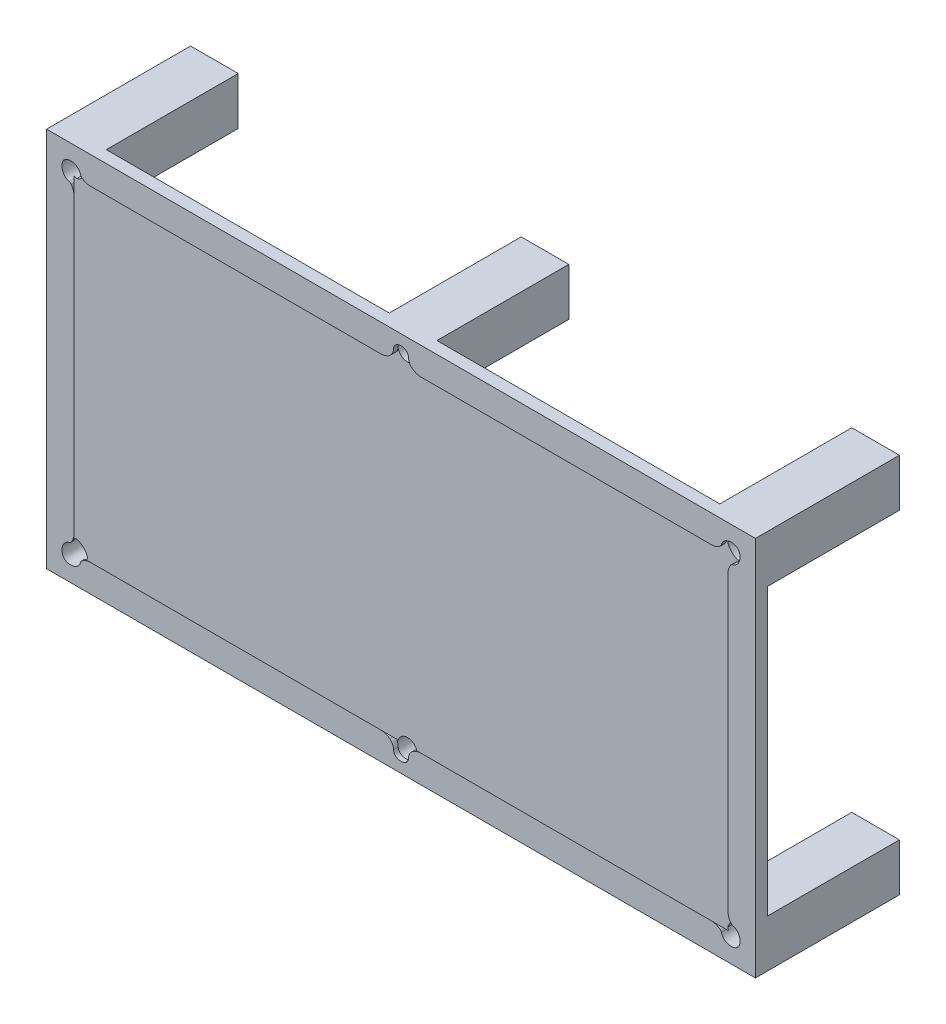
SolidWorks part; units mm, degrees
ref_plane "Płaszczyzna przednia" through (0, 0, 0) normal (0, 0, 1) x (1, 0, 0)
ref_plane "Płaszczyzna górna" through (0, 0, 0) normal (0, 1, 0) x (1, 0, 0)
ref_plane "Płaszczyzna prawa" through (0, 0, 0) normal (1, 0, 0) x (0, 0, -1)
sketch "Szkic1" plane through (0, 0, 0) normal (0, 0, 1) x (1, 0, 0)
  line L1 (-1934.5, -1039) -> (1934.5, -1039)
  line L2 (-1934.5, -1039) -> (-1934.5, 1039)
  line L3 (-1934.5, 1039) -> (1934.5, 1039)
  line L4 (1934.5, -1039) -> (1934.5, 1039)
  line L5 (-1934.5, -1039) -> (1934.5, 1039) construction
  line L6 (-1934.5, 1039) -> (1934.5, -1039) construction
  line L7 (-1784.5, -889) -> (1784.5, -889)
  line L8 (-1784.5, -889) -> (-1784.5, 889)
  line L9 (-1784.5, 889) -> (1784.5, 889)
  line L10 (1784.5, -889) -> (1784.5, 889)
  line L11 (-1784.5, -889) -> (1784.5, 889) construction
  line L12 (-1784.5, 889) -> (1784.5, -889) construction
  point P0 (0, 0)
  point P6 (0, 0)
  dimension "D1" = 3869
  dimension "D2" = 2078
  dimension "D3" = 3569
  dimension "D4" = 1778
extrude "Dodanie-wyciągnięcie1" add sketch "Szkic1" along normal blind 36
sketch "Szkic2" plane through (0, 0, 0) normal (0, 0, -1) x (-1, 0, 0)
  line L1 (-1934.5, -1039) -> (1934.5, -1039)
  line L2 (-1934.5, -1039) -> (-1934.5, 1039)
  line L3 (-1934.5, 1039) -> (1934.5, 1039)
  line L4 (1934.5, -1039) -> (1934.5, 1039)
  line L5 (-1934.5, -1039) -> (1934.5, 1039) construction
  line L6 (-1934.5, 1039) -> (1934.5, -1039) construction
  point P0 (0, 0)
chamfer "Sfazowanie1" distance 36 angle 45 4 edges at (-1784.5, 0, 0) (0, -889, 0) (1784.5, 0, 0) (0, 889, 0)
sketch "Szkic3" plane through (0, 0, 0) normal (0, 0, -1) x (-1, 0, 0)
  line L1 (-1934.5, -1039) -> (1934.5, -1039)
  line L2 (-1934.5, -1039) -> (-1934.5, 1039)
  line L3 (-1934.5, 1039) -> (1934.5, 1039)
  line L4 (1934.5, -1039) -> (1934.5, 1039)
  line L5 (-1934.5, -1039) -> (1934.5, 1039) construction
  line L6 (-1934.5, 1039) -> (1934.5, -1039) construction
  point P1 (0, 0)
extrude "Dodanie-wyciągnięcie3" add sketch "Szkic3" along normal blind 30
sketch "Szkic5" plane through (0, 0, -30) normal (0, 0, -1) x (-1, 0, 0)
  line L1 (-1934.5, 1039) -> (-1674.5, 1039)
  line L2 (-1934.5, 1039) -> (-1934.5, 779)
  line L3 (-1934.5, 779) -> (-1674.5, 779)
  line L4 (-1674.5, 1039) -> (-1674.5, 779)
  line L5 (1934.5, 1039) -> (1674.5, 1039)
  line L6 (1934.5, 1039) -> (1934.5, 779)
  line L7 (1934.5, 779) -> (1674.5, 779)
  line L8 (1674.5, 1039) -> (1674.5, 779)
  line L9 (1934.5, -1039) -> (1674.5, -1039)
  line L10 (1934.5, -1039) -> (1934.5, -779)
  line L11 (1934.5, -779) -> (1674.5, -779)
  line L12 (1674.5, -1039) -> (1674.5, -779)
  line L13 (-1934.5, -1039) -> (-1674.5, -1039)
  line L14 (-1934.5, -1039) -> (-1934.5, -779)
  line L15 (-1934.5, -779) -> (-1674.5, -779)
  line L16 (-1674.5, -1039) -> (-1674.5, -779)
  dimension "D1" = 260
  dimension "D2" = 260
  dimension "D3" = 260
  dimension "D4" = 260
  dimension "D5" = 260
  dimension "D6" = 260
  dimension "D7" = 260
  dimension "D8" = 260
extrude "Dodanie-wyciągnięcie4" add sketch "Szkic5" along normal blind 720
sketch "Szkic6" plane through (0, 0, 36) normal (0, 0, 1) x (1, 0, 0)
  line L0 (-1694.21, -889) -> (-1694.21, -936.63)
  line L1 (-1784.5, -889) -> (1784.5, -889) construction
  line L2 (-1694.21, -936.63) -> (-1832.13, -936.63)
  line L3 (-1832.13, -936.63) -> (-1832.13, -798.71)
  line L4 (-1832.13, -798.71) -> (-1784.5, -798.71)
  line L5 (-1784.5, 889) -> (-1784.5, -889) construction
  line L6 (-1675.92, -889) -> (-1675.92, -998.73)
  line L7 (-1832.13, -936.63) -> (-1832.13, -1039)
  line L8 (1934.5, -1039) -> (-1934.5, -1039) construction
  line L9 (-1832.13, -936.63) -> (-1934.5, -936.63)
  line L10 (-1934.5, -1039) -> (-1934.5, 1039) construction
  line L11 (-1694.21, -889) -> (-1694.21, -965.2)
  line L12 (-1675.92, -998.73) -> (-1832.13, -998.73)
  line L13 (-1675.92, -998.73) -> (-1735.7757, -889)
  line L14 (-1735.7757, -889) -> (-1694.21, -889)
  line L15 (-1784.5, -780.42) -> (-1894.23, -780.42)
  line L16 (-1894.23, -780.42) -> (-1894.23, -936.63)
  line L17 (-1784.5, -798.71) -> (-1860.7, -798.71)
  line L18 (-1894.23, -780.42) -> (-1784.5, -840.2757)
  line L19 (-1832.13, -847.73) -> (-1832.13, -798.71)
  line L20 (0, 889) -> (0, -889) construction
  line L21 (1784.5, 889) -> (-1784.5, 889) construction
  line L22 (-1934.5, 0) -> (1784.5, 0) construction
  line L23 (1784.5, -889) -> (1784.5, 889) construction
  line L24 (1832.13, -847.73) -> (1832.13, -798.71)
  line L25 (1894.23, -780.42) -> (1784.5, -840.2757)
  line L26 (1784.5, -798.71) -> (1860.7, -798.71)
  line L27 (1894.23, -780.42) -> (1894.23, -936.63)
  line L28 (1784.5, -780.42) -> (1894.23, -780.42)
  line L29 (1735.7757, -889) -> (1694.21, -889)
  line L30 (1675.92, -998.73) -> (1735.7757, -889)
  line L31 (1675.92, -998.73) -> (1832.13, -998.73)
  line L32 (1694.21, -889) -> (1694.21, -965.2)
  line L33 (1832.13, -936.63) -> (1934.5, -936.63)
  line L34 (1832.13, -936.63) -> (1832.13, -1039)
  line L35 (1675.92, -889) -> (1675.92, -998.73)
  line L36 (1832.13, -798.71) -> (1784.5, -798.71)
  line L37 (1832.13, -936.63) -> (1832.13, -798.71)
  line L38 (1694.21, -889) -> (1694.21, -936.63)
  line L39 (1694.21, 889) -> (1694.21, 936.63)
  line L40 (1832.13, 936.63) -> (1832.13, 798.71)
  line L41 (1832.13, 798.71) -> (1784.5, 798.71)
  line L42 (1675.92, 889) -> (1675.92, 998.73)
  line L43 (1832.13, 936.63) -> (1832.13, 1039)
  line L44 (1832.13, 936.63) -> (1934.5, 936.63)
  line L45 (1694.21, 889) -> (1694.21, 965.2)
  line L46 (1675.92, 998.73) -> (1832.13, 998.73)
  line L47 (1675.92, 998.73) -> (1735.7757, 889)
  line L48 (1735.7757, 889) -> (1694.21, 889)
  line L49 (1784.5, 780.42) -> (1894.23, 780.42)
  line L50 (1894.23, 780.42) -> (1894.23, 936.63)
  line L51 (1784.5, 798.71) -> (1860.7, 798.71)
  line L52 (1894.23, 780.42) -> (1784.5, 840.2757)
  line L53 (1832.13, 847.73) -> (1832.13, 798.71)
  line L54 (-1832.13, 847.73) -> (-1832.13, 798.71)
  line L55 (-1894.23, 780.42) -> (-1784.5, 840.2757)
  line L56 (-1784.5, 798.71) -> (-1860.7, 798.71)
  line L57 (-1894.23, 780.42) -> (-1894.23, 936.63)
  line L58 (-1784.5, 780.42) -> (-1894.23, 780.42)
  line L59 (-1735.7757, 889) -> (-1694.21, 889)
  line L60 (-1675.92, 998.73) -> (-1735.7757, 889)
  line L61 (-1675.92, 998.73) -> (-1832.13, 998.73)
  line L62 (-1694.21, 889) -> (-1694.21, 965.2)
  line L63 (-1832.13, 936.63) -> (-1934.5, 936.63)
  line L64 (-1832.13, 936.63) -> (-1832.13, 1039)
  line L65 (-1675.92, 889) -> (-1675.92, 998.73)
  line L66 (-1832.13, 798.71) -> (-1784.5, 798.71)
  line L67 (-1832.13, 936.63) -> (-1832.13, 798.71)
  line L68 (-1694.21, 936.63) -> (-1832.13, 936.63)
  line L69 (-1694.21, 889) -> (-1694.21, 936.63)
  line L70 (-1784.5, 798.71) -> (-1784.5, 861.5661)
  line L71 (-1694.21, 889) -> (-1757.0661, 889)
  line L72 (-1784.5, -798.71) -> (-1784.5, -861.5661)
  line L73 (-1694.21, -889) -> (-1757.0661, -889)
  line L74 (1694.21, -889) -> (1757.0661, -889)
  line L75 (1784.5, -798.71) -> (1784.5, -861.5661)
  line L76 (1694.21, 889) -> (1757.0661, 889)
  line L77 (1784.5, 798.71) -> (1784.5, 861.5661)
  arc A0 (-1694.21, -889) -> (-1730.6999, -898.3051) centre (-1694.21, -965.2) ccw
  arc A1 (-1730.6999, -898.3051) -> (-1747.4772, -909.48) centre (-1675.92, -998.73) ccw
  arc A2 (-1743.23, -936.63) -> (-1832.13, -847.73) centre (-1832.13, -936.63) ccw
  arc A3 (-1793.8051, -835.1999) -> (-1784.5, -798.71) centre (-1860.7, -798.71) ccw
  arc A4 (1743.23, -936.63) -> (1832.13, -847.73) centre (1832.13, -936.63) cw
  arc A5 (-1804.98, -851.9772) -> (-1793.8051, -835.1999) centre (-1894.23, -780.42) ccw
  arc A6 (1804.98, -851.9772) -> (1793.8051, -835.1999) centre (1894.23, -780.42) cw
  arc A7 (1793.8051, -835.1999) -> (1784.5, -798.71) centre (1860.7, -798.71) cw
  arc A8 (1730.6999, -898.3051) -> (1747.4772, -909.48) centre (1675.92, -998.73) cw
  arc A9 (1694.21, -889) -> (1730.6999, -898.3051) centre (1694.21, -965.2) cw
  arc A10 (1694.21, 889) -> (1730.6999, 898.3051) centre (1694.21, 965.2) ccw
  arc A11 (1730.6999, 898.3051) -> (1747.4772, 909.48) centre (1675.92, 998.73) ccw
  arc A12 (1793.8051, 835.1999) -> (1784.5, 798.71) centre (1860.7, 798.71) ccw
  arc A13 (1804.98, 851.9772) -> (1793.8051, 835.1999) centre (1894.23, 780.42) ccw
  arc A14 (-1804.98, 851.9772) -> (-1793.8051, 835.1999) centre (-1894.23, 780.42) cw
  arc A15 (1743.23, 936.63) -> (1832.13, 847.73) centre (1832.13, 936.63) ccw
  arc A16 (-1793.8051, 835.1999) -> (-1784.5, 798.71) centre (-1860.7, 798.71) cw
  arc A17 (-1743.23, 936.63) -> (-1832.13, 847.73) centre (-1832.13, 936.63) cw
  arc A18 (-1730.6999, 898.3051) -> (-1747.4772, 909.48) centre (-1675.92, 998.73) cw
  arc A19 (-1694.21, 889) -> (-1730.6999, 898.3051) centre (-1694.21, 965.2) cw
  line M5 (1784.5, 889) -> (1784.5, -889)
  line M6 (1784.5, -889) -> (-1784.5, -889)
  line M7 (-1784.5, -889) -> (-1784.5, 889)
  line M8 (-1784.5, 889) -> (1784.5, 889)
  dimension "D8" = 177.8
  dimension "D1" = 47.63
  dimension "D2" = 47.63
  dimension "D3" = 137.92
  dimension "D4" = 137.92
  dimension "D5" = 109.73
  dimension "D6" = 76.2
  dimension "D7" = 156.21
  dimension "D9" = 109.73
  dimension "D10" = 156.21
  dimension "D11" = 76.2
extrude "Wytnij-wyciągnięcie1" cut sketch "Szkic6" against normal blind 35 contours A2 A1 L13 M6 | A0 L13 M6 | A5 A2 L18 M7 | A3 L18 M7 | L60 A18 A17 M8 | A19 L60 M8 | L55 A16 M7 | A17 A14 L55 M7 | A10 L47 M8 | A15 A11 L47 M8 | A15 L52 A13 M5 | A12 L52 M5 | A9 L30 M6 | L30 A8 A4 M6 | A4 A6 L25 M5 | L25 A7 M5 region at (-1723.5799, -891.82, 36) region at (-1743.6941, -896.6294, 36) region at (-1792.1294, -848.1941, 36) region at (1723.5799, -891.82, 36) region at (-1787.32, -828.0799, 36) region at (1743.6941, -896.6294, 36) region at (1792.1294, -848.1941, 36) region at (1787.32, -828.0799, 36) region at (-1787.32, 828.0799, 36) region at (-1792.1294, 848.1941, 36) region at (1787.32, 828.0799, 36) region at (-1743.6941, 896.6294, 36) region at (1792.1294, 848.1941, 36) region at (-1723.5799, 891.82, 36) region at (1743.6941, 896.6294, 36) region at (1723.5799, 891.82, 36)
sketch "Szkic7" plane through (0, 0, 36) normal (0, 0, 1) x (1, 0, 0)
  line L0 (-1784.5, -861.5661) -> (-1757.0661, -889)
  line L1 (0, 889) -> (0, -889) construction
  line L2 (-1770.783, -875.283) -> (-1837.9582, -942.4582) construction
  line L3 (-1784.5, -861.5661) -> (-1848.1396, -925.2057) construction
  line L4 (-1757.0661, -889) -> (-1820.7057, -952.6396) construction
  line L5 (1694.21, 889) -> (-1694.21, 889) construction
  line L6 (-1694.21, -889) -> (1694.21, -889) construction
  line L7 (-1784.5, 0) -> (1784.5, 0) construction
  line L8 (-1784.5, 798.71) -> (-1784.5, -798.71) construction
  line L9 (1784.5, -798.71) -> (1784.5, 798.71) construction
  line L10 (1757.0661, -889) -> (1820.7057, -952.6396) construction
  line L11 (1784.5, -861.5661) -> (1848.1396, -925.2057) construction
  line L12 (1770.783, -875.283) -> (1837.9582, -942.4582) construction
  line L13 (1784.5, -861.5661) -> (1757.0661, -889)
  line L14 (1770.783, 875.283) -> (1837.9582, 942.4582) construction
  line L15 (1784.5, 861.5661) -> (1848.1396, 925.2057) construction
  line L16 (1757.0661, 889) -> (1820.7057, 952.6396) construction
  line L17 (-1757.0661, 889) -> (-1820.7057, 952.6396) construction
  line L18 (-1784.5, 861.5661) -> (-1848.1396, 925.2057) construction
  line L19 (-1770.783, 875.283) -> (-1837.9582, 942.4582) construction
  line L20 (1784.5, 861.5661) -> (1757.0661, 889)
  line L21 (-1784.5, 861.5661) -> (-1757.0661, 889)
  spline S0 degree 3 poles (-1804.98, -851.9772) (-1778.2039, -860.2968) (-1755.7968, -882.7039) (-1747.4772, -909.48) knots 0 0 0 0 1 1 1 1
  spline S1 degree 3 poles (-1804.98, -851.9772) (-1851.8075, -858.2422) (-1873.1415, -977.6415) (-1753.7422, -956.3075) (-1747.4772, -909.48) knots 0 0 0 0 0.5 1 1 1 1
  spline S2 degree 3 poles (1804.98, -851.9772) (1851.8075, -858.2422) (1873.1415, -977.6415) (1753.7422, -956.3075) (1747.4772, -909.48) knots 0 0 0 0 0.5 1 1 1 1
  spline S3 degree 3 poles (1804.98, -851.9772) (1778.2039, -860.2968) (1755.7968, -882.7039) (1747.4772, -909.48) knots 0 0 0 0 1 1 1 1
  spline S4 degree 3 poles (1804.98, 851.9772) (1778.2039, 860.2968) (1755.7968, 882.7039) (1747.4772, 909.48) knots 0 0 0 0 1 1 1 1
  spline S5 degree 3 poles (1804.98, 851.9772) (1851.8075, 858.2422) (1873.1415, 977.6415) (1753.7422, 956.3075) (1747.4772, 909.48) knots 0 0 0 0 0.5 1 1 1 1
  spline S6 degree 3 poles (-1804.98, 851.9772) (-1851.8075, 858.2422) (-1873.1415, 977.6415) (-1753.7422, 956.3075) (-1747.4772, 909.48) knots 0 0 0 0 0.5 1 1 1 1
  spline S7 degree 3 poles (-1804.98, 851.9772) (-1778.2039, 860.2968) (-1755.7968, 882.7039) (-1747.4772, 909.48) knots 0 0 0 0 1 1 1 1
  arc M6 (1804.98, -851.9772) -> (1784.5, -861.5661) centre (1832.13, -936.63) ccw
  line M7 (1784.5, -861.5661) -> (1784.5, -889)
  line M8 (1784.5, -889) -> (1757.0661, -889)
  arc M9 (1757.0661, -889) -> (1747.4772, -909.48) centre (1832.13, -936.63) ccw
  arc M15 (-1747.4772, -909.48) -> (-1757.0661, -889) centre (-1832.13, -936.63) ccw
  line M16 (-1757.0661, -889) -> (-1784.5, -889)
  line M17 (-1784.5, -889) -> (-1784.5, -861.5661)
  arc M18 (-1784.5, -861.5661) -> (-1804.98, -851.9772) centre (-1832.13, -936.63) ccw
  arc M24 (-1804.98, 851.9772) -> (-1784.5, 861.5661) centre (-1832.13, 936.63) ccw
  line M25 (-1784.5, 861.5661) -> (-1784.5, 889)
  line M26 (-1784.5, 889) -> (-1757.0661, 889)
  arc M27 (-1757.0661, 889) -> (-1747.4772, 909.48) centre (-1832.13, 936.63) ccw
  arc M33 (1747.4772, 909.48) -> (1757.0661, 889) centre (1832.13, 936.63) ccw
  line M34 (1757.0661, 889) -> (1784.5, 889)
  line M35 (1784.5, 889) -> (1784.5, 861.5661)
  arc M36 (1784.5, 861.5661) -> (1804.98, 851.9772) centre (1832.13, 936.63) ccw
  dimension "D1" = 95
  dimension "D2" = 90
  dimension "D3" = 90
extrude "Wytnij-wyciągnięcie2" cut sketch "Szkic7" against normal blind 652 contours S6 M24 M25 M26 M27 | L21 M25 M26 | L21 S7 | S5 M36 M33 M34 M35 | L20 M35 M34 | S2 M6 M7 M8 M9 | L13 M7 M8 | L13 S3 | S1 M18 M15 M16 M17 | L0 M17 M16 | S4 S5 | S0 S1 region at (-1775.3554, -879.8554, 36) region at (-1803.3468, -907.8479, 36) region at (1775.3554, -879.8554, 36) region at (1770.1919, -874.6919, 36) region at (1803.3468, -907.8436, 36) region at (1775.3554, 879.8554, 36) region at (1803.3468, 907.8436, 36) region at (-1775.3554, 879.8554, 36) region at (-1770.1919, 874.6919, 36) region at (-1803.3468, 907.8479, 36)
fillet "Zaokrąglenie1" radius 20 8 edges at (-1804.98, 851.9772, 25.76) (-1747.4772, 909.48, 25.76) (-1804.98, -851.9772, 25.76) (-1747.4772, -909.48, 25.76) (1747.4772, -909.48, 25.76) (1804.98, -851.9772, 25.76) (1804.98, 851.9772, 25.76) (1747.4772, 909.48, 25.76)
sketch "Szkic8" plane through (0, 0, 36) normal (0, 0, 1) x (1, 0, 0)
  line L0 (0, 1039) -> (0, -1039) construction
  line L1 (1934.5, 1039) -> (-1934.5, 1039) construction
  line L2 (1934.5, -1039) -> (-1934.5, -1039) construction
  line L3 (-1934.5, 0) -> (1934.5, 0) construction
  line L4 (-1934.5, -1039) -> (-1934.5, 1039) construction
  line L5 (1934.5, -1039) -> (1934.5, 1039) construction
  line L6 (110.34, -889) -> (-110.34, -889)
  line L7 (-1694.21, -889) -> (1694.21, -889) construction
  line L8 (-110.34, -889) -> (-110.34, -936.75)
  line L9 (-110.34, -936.75) -> (-110.34, -947.88)
  line L10 (-110.34, -936.75) -> (-110.34, -968.5)
  line L11 (94.46, -947.88) -> (-94.46, -947.88)
  line L12 (-110.34, -968.5) -> (-61.8326, -905.5137)
  line L13 (0, -889) -> (0, -940.81)
  line L14 (0, -940.81) -> (-43.0316, -909.5457)
  line L15 (-43.0316, -909.5457) -> (-49.53, -918.8843)
  line L16 (43.0316, -909.5457) -> (49.53, -918.8843)
  line L17 (0, -940.81) -> (43.0316, -909.5457)
  line L18 (110.34, -968.5) -> (61.8326, -905.5137)
  line L19 (110.34, -936.75) -> (110.34, -968.5)
  line L20 (110.34, -936.75) -> (110.34, -947.88)
  line L21 (110.34, -889) -> (110.34, -936.75)
  line L22 (110.34, 889) -> (110.34, 936.75)
  line L23 (110.34, 936.75) -> (110.34, 947.88)
  line L24 (110.34, 936.75) -> (110.34, 968.5)
  line L25 (110.34, 968.5) -> (61.8326, 905.5137)
  line L26 (0, 940.81) -> (43.0316, 909.5457)
  line L27 (43.0316, 909.5457) -> (49.53, 918.8843)
  line L28 (-43.0316, 909.5457) -> (-49.53, 918.8843)
  line L29 (0, 940.81) -> (-43.0316, 909.5457)
  line L30 (0, 889) -> (0, 940.81)
  line L31 (-110.34, 968.5) -> (-61.8326, 905.5137)
  line L32 (94.46, 947.88) -> (-94.46, 947.88)
  line L33 (-110.34, 936.75) -> (-110.34, 968.5)
  line L34 (-110.34, 936.75) -> (-110.34, 947.88)
  line L35 (-110.34, 889) -> (-110.34, 936.75)
  line L36 (110.34, 889) -> (-110.34, 889)
  arc A0 (-61.8326, -905.5137) -> (-110.34, -889) centre (-110.34, -968.5) ccw
  arc A1 (-40.9861, -947.88) -> (-61.8326, -905.5137) centre (-94.46, -947.88) ccw
  arc A2 (43.0316, -909.5457) -> (-43.0316, -909.5457) centre (0, -940.81) ccw
  arc A3 (40.9861, -947.88) -> (61.8326, -905.5137) centre (94.46, -947.88) cw
  arc A4 (61.8326, -905.5137) -> (110.34, -889) centre (110.34, -968.5) cw
  arc A5 (61.8326, 905.5137) -> (110.34, 889) centre (110.34, 968.5) ccw
  arc A6 (40.9861, 947.88) -> (61.8326, 905.5137) centre (94.46, 947.88) ccw
  arc A7 (43.0316, 909.5457) -> (-43.0316, 909.5457) centre (0, 940.81) cw
  arc A8 (-40.9861, 947.88) -> (-61.8326, 905.5137) centre (-94.46, 947.88) cw
  arc A9 (-61.8326, 905.5137) -> (-110.34, 889) centre (-110.34, 968.5) cw
  point P33 (0, -947.88)
  point P55 (0, 947.88)
  line M11 (-1694.21, 889) -> (1694.21, 889)
  line M27 (1694.21, -889) -> (-1694.21, -889)
  dimension "D8" = 106.38
  dimension "D1" = 110.34
  dimension "D2" = 47.75
  dimension "D3" = 11.13
  dimension "D4" = 31.75
  dimension "D5" = 94.46
  dimension "D6" = 51.81
  dimension "D7" = 54
  dimension "D9" = 49.53
extrude "Wytnij-wyciągnięcie3" cut sketch "Szkic8" against normal blind 35 contours A2 A0 A1 L15 M27 | L6 A2 L14 L13 | L17 A2 L6 L13 | A3 A4 A2 L16 M27 | L11 A3 L16 L17 L14 L15 A1 | A8 A9 A7 L28 M11 | L32 A8 L28 L29 L26 L27 A6 | A7 L36 L30 L29 | A7 L26 L30 M11 | L27 A7 L36 A5 A6 region at (53.4142, -897.5282, 36) region at (15.6015, -910.5555, 36) region at (-15.6015, -910.5555, 36) region at (45.4089, -914.8217, 36) region at (-53.4142, -897.5282, 36) region at (53.4142, 897.5282, 36) region at (15.6015, 910.5555, 36) region at (-15.6015, 910.5555, 36) region at (22.1401, 926.0372, 36) region at (-53.4142, 897.5282, 36)
sketch "Szkic11" plane through (0, 0, 0) normal (0, 0, 1) x (1, 0, 0)
  circle A0 centre (0, -940.81) radius 53.19
  circle A1 centre (0, 940.81) radius 53.19
  dimension "D1" = 106.38
  dimension "D2" = 106.38
extrude "Wytnij-wyciągnięcie4" cut sketch "Szkic11" against normal blind 594 and the other way blind 10
sketch "Szkic12" plane through (0, 0, 36) normal (0, 0, 1) x (1, 0, 0)
  line L0 (-40.9861, 947.88) -> (0, 947.88)
  line L1 (0, 947.88) -> (40.9861, 947.88)
  line L2 (-20.4931, 947.88) -> (-20.4931, 977.88)
  line L3 (20.4931, 947.88) -> (20.4931, 977.88)
  line L4 (-1934.5, 0) -> (1934.5, 0) construction
  line L5 (20.4931, -947.88) -> (20.4931, -977.88)
  line L6 (-20.4931, -947.88) -> (-20.4931, -977.88)
  line L7 (0, -947.88) -> (40.9861, -947.88)
  line L8 (-40.9861, -947.88) -> (0, -947.88)
  spline S0 degree 3 poles (-40.9861, 947.88) (-37.9369, 993.8602) (37.9369, 993.8602) (40.9861, 947.88) knots 0 0 0 0 1 1 1 1
  spline S1 degree 3 poles (-40.9861, -947.88) (-37.9369, -993.8602) (37.9369, -993.8602) (40.9861, -947.88) knots 0 0 0 0 1 1 1 1
  line M8 (-40.9861, 947.88) -> (40.9861, 947.88)
  line M30 (40.9861, -947.88) -> (-40.9861, -947.88)
  dimension "D1" = 30
  dimension "D2" = 30
extrude "Wytnij-wyciągnięcie5" cut sketch "Szkic12" against normal blind 511 contours S0 L2 M8 | S0 L2 L0 L3 M8 | S0 L3 L1 | S1 L6 M30 | L6 S1 L5 M30 | L5 S1 M30 region at (-28.8113, 959.6543, 36) region at (0, 964.4263, 36) region at (28.8113, 959.6543, 36) region at (28.8113, -959.6543, 36) region at (0, -964.4263, 36) region at (-28.8113, -959.6543, 36)
sketch "Szkic13" plane through (0, 0, -30) normal (0, 0, -1) x (-1, 0, 0)
  line L1 (0, 1039) -> (0, 909)
  line L2 (0, 1039) -> (0, -1039) construction
  line L3 (-1934.5, 1039) -> (1934.5, 1039) construction
  line L4 (-130, 779) -> (130, 779)
  line L5 (-130, 779) -> (-130, 1039)
  line L6 (-130, 1039) -> (130, 1039)
  line L7 (130, 779) -> (130, 1039)
  line L8 (-130, 779) -> (130, 1039) construction
  line L9 (-130, 1039) -> (130, 779) construction
  line L10 (0, -1039) -> (0, -909)
  line L11 (-1934.5, -1039) -> (1934.5, -1039) construction
  line L13 (-130, -779) -> (130, -779)
  line L14 (-130, -779) -> (-130, -1039)
  line L15 (-130, -1039) -> (130, -1039)
  line L16 (130, -779) -> (130, -1039)
  line L17 (-130, -779) -> (130, -1039) construction
  line L18 (-130, -1039) -> (130, -779) construction
  circle M1 centre (0, -940.81) radius 53.19
  line M3 (-1674.5, -1039) -> (1674.5, -1039)
  line M9 (1674.5, 1039) -> (-1674.5, 1039)
  circle M14 centre (0, 940.81) radius 53.19
  dimension "D1" = 130
  dimension "D2" = 260
  dimension "D3" = 130
  dimension "D4" = 260
extrude "Dodanie-wyciągnięcie5" add sketch "Szkic13" along normal blind 720 contours L4 L7 L5 M9 M14 | L16 L13 L14 M3 M1 region at (-65, 1035.323, -30) region at (65, -1035.323, -30)
